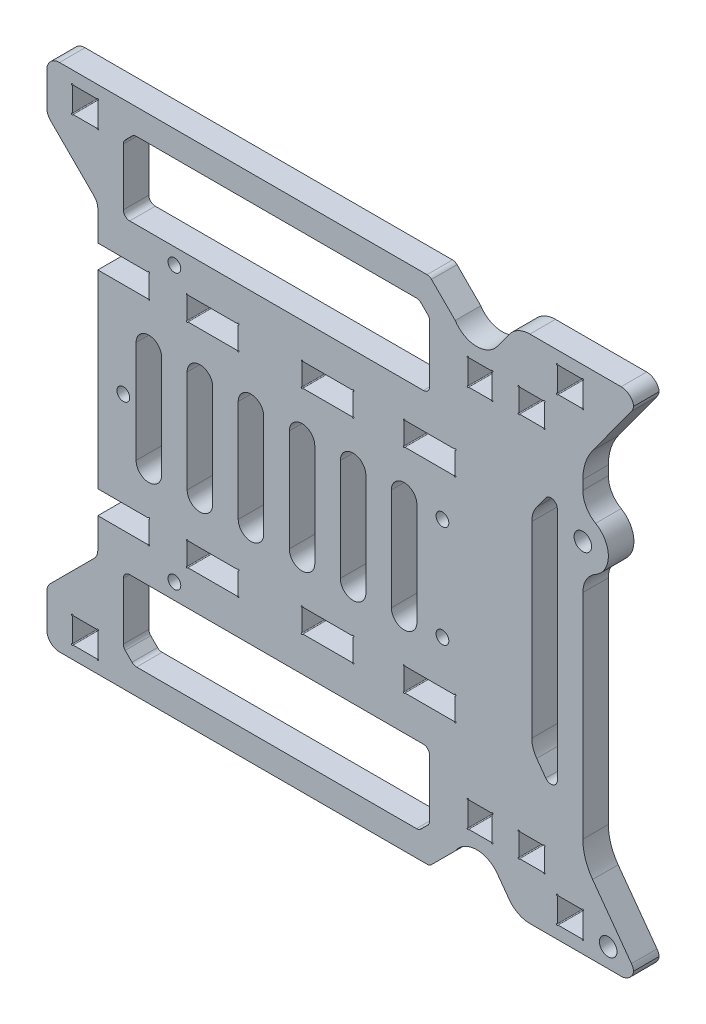
SolidWorks part; units mm, degrees
ref_plane "Front Plane" through (0, 0, 0) normal (0, 0, 1) x (1, 0, 0)
ref_plane "Top Plane" through (0, 0, 0) normal (0, 1, 0) x (1, 0, 0)
ref_plane "Right Plane" through (0, 0, 0) normal (1, 0, 0) x (0, 0, -1)
sketch "Sketch1" plane through (0, 0, 0) normal (0, 0, 1) x (1, 0, 0)
  line L0 (83.672, 0) -> (-43.8164, 0) construction
  line L1 (10.525, 38.1) -> (10.525, -38.1) construction
  line L2 (-27.575, 38.1) -> (48.625, 38.1)
  line L3 (99.425, -63.5) -> (99.425, -60.325)
  line L4 (99.425, -60.325) -> (74.025, -25.4)
  line L5 (-27.575, -63.5) -> (48.625, -63.5)
  line L6 (-27.575, 38.1) -> (-27.575, 54.5197)
  line L7 (48.625, 38.1) -> (48.625, 54.5197)
  line L8 (-24.9447, 57.15) -> (45.9947, 57.15)
  line L9 (-27.575, 63.5) -> (48.625, 63.5)
  line L10 (-33.925, 57.15) -> (-33.925, -57.15)
  line L11 (-27.575, 63.5) -> (-33.925, 57.15)
  line L12 (-24.9447, 57.15) -> (-27.575, 54.5197)
  line L13 (99.425, 63.5) -> (99.425, 60.325)
  line L14 (-23.0849, 59.0099) -> (-29.4349, 52.6599) construction
  line L15 (99.425, 60.325) -> (74.025, 25.4)
  line L16 (74.025, 25.4) -> (74.025, -25.4)
  line L17 (48.625, -38.1) -> (48.625, -54.5197)
  line L18 (-27.575, -38.1) -> (48.625, -38.1)
  line L19 (-24.9447, -57.15) -> (45.9947, -57.15)
  line L20 (-24.9447, -57.15) -> (-27.575, -54.5197)
  line L21 (-27.575, -38.1) -> (-27.575, -54.5197)
  line L22 (-27.575, -63.5) -> (-33.925, -57.15)
  line L23 (48.625, -63.5) -> (54.975, -57.15)
  line L24 (48.625, 63.5) -> (54.975, 57.15)
  line L25 (70.3271, -63.5) -> (99.425, -63.5)
  line L26 (45.9947, 57.15) -> (48.625, 54.5197)
  line L27 (45.9947, -57.15) -> (48.625, -54.5197)
  line L28 (70.3271, 63.5) -> (65.7089, 57.15)
  line L29 (70.3271, 63.5) -> (99.425, 63.5)
  line L30 (78.8831, 75.2646) -> (53.4831, 40.3396) construction
  line L31 (54.975, -42.3909) -> (54.975, -57.15)
  line L32 (70.3271, -63.5) -> (65.7089, -57.15)
  line L34 (48.625, -63.5) -> (54.975, -57.15)
  line L35 (65.7089, 57.15) -> (54.975, 42.3909)
  line L36 (54.975, 42.3909) -> (54.975, 57.15)
  line L37 (65.7089, -57.15) -> (54.975, -42.3909)
  point P7 (-27.575, 0)
  point P21 (74.025, 0)
  point P22 (-33.925, 0)
  dimension "D1" = 25.4
  dimension "D2" = 76.2
  dimension "D3" = 127
  dimension "D4" = 6.35
  dimension "D7" = 3.175
  dimension "D8" = 25.4
  dimension "D9" = 25.4
  dimension "D6" = 6.35
extrude "Boss-Extrude1" add sketch "Sketch1" along normal blind 6.35
fillet "Fillet1" radius 6.35 4 edges at (70.3271, 63.5, 3.175) (70.3271, -63.5, 3.175) (54.975, -42.3909, 3.175) (54.975, 42.3909, 3.175)
fillet "Fillet3" radius 3.175 4 edges at (99.425, 63.5, 3.175) (99.425, 60.325, 3.175) (99.425, -60.325, 3.175) (99.425, -63.5, 3.175)
fillet "Fillet4" radius 6.35 2 edges at (74.025, -25.4, 3.175) (74.025, 25.4, 3.175)
fillet "Fillet7" radius 1.5875 4 edges at (-27.575, -38.1, 3.175) (48.625, -38.1, 3.175) (48.625, 38.1, 3.175) (-27.575, 38.1, 3.175)
fillet "Fillet8" radius 1.5875 2 edges at (48.625, -63.5, 3.175) (48.625, 63.5, 3.175)
fillet "Fillet9" radius 1.5875 8 edges at (-27.575, 54.5197, 3.175) (-24.9447, 57.15, 3.175) (-27.575, -54.5197, 3.175) (-24.9447, -57.15, 3.175) (45.9947, -57.15, 3.175) (48.625, -54.5197, 3.175) (48.625, 54.5197, 3.175) (45.9947, 57.15, 3.175)
sketch "Sketch2" plane through (0, 0, 6.35) normal (0, 0, 1) x (1, 0, 0)
  line L0 (-33.925, 0) -> (74.025, 0) construction
  line L1 (-33.925, 57.15) -> (-33.925, -57.15) construction
  line L2 (74.025, 23.3351) -> (74.025, -23.3351) construction
  line L3 (48.625, 39.6875) -> (48.625, 53.8622) construction
  line L4 (58.3484, 50.8) -> (63.9714, 50.8)
  line L5 (58.15, 50.6016) -> (58.15, 44.6484)
  line L6 (58.3484, 44.45) -> (63.9714, 44.45)
  line L7 (64.1698, 50.6016) -> (64.1698, 44.6484)
  line L8 (64.1698, -50.6016) -> (64.1698, -44.6484)
  line L9 (58.3484, -50.8) -> (63.9714, -50.8)
  line L10 (58.15, -50.6016) -> (58.15, -44.6484)
  line L11 (58.3484, -44.45) -> (63.9714, -44.45)
  arc A0 (58.3484, 50.8) -> (58.15, 50.6016) centre (58.15, 50.8) ccw
  arc A1 (64.1698, 50.6016) -> (63.9714, 50.8) centre (64.1698, 50.8) ccw
  arc A2 (63.9714, 44.45) -> (64.1698, 44.6484) centre (64.1698, 44.45) ccw
  arc A3 (58.15, 44.6484) -> (58.3484, 44.45) centre (58.15, 44.45) ccw
  arc A4 (63.9714, -44.45) -> (64.1698, -44.6484) centre (64.1698, -44.45) cw
  arc A5 (64.1698, -50.6016) -> (63.9714, -50.8) centre (64.1698, -50.8) cw
  arc A6 (58.3484, -50.8) -> (58.15, -50.6016) centre (58.15, -50.8) cw
  arc A7 (58.15, -44.6484) -> (58.3484, -44.45) centre (58.15, -44.45) cw
  point P10 (48.625, 46.7748)
  dimension "D5" = 0.3969
  dimension "D6" = 0.3969
  dimension "D7" = 0.3969
  dimension "D8" = 0.3969
  dimension "D1" = 6.0198
  dimension "D2" = 6.35
  dimension "D3" = 50.8
  dimension "D4" = 9.525
extrude "Cut-Extrude1" cut sketch "Sketch2" against normal through all
sketch "Sketch5" plane through (0, 0, 6.35) normal (0, 0, 1) x (1, 0, 0)
  line L0 (-33.925, 29.3675) -> (74.025, 29.3675) construction
  line L1 (-33.925, 57.15) -> (-33.925, -57.15) construction
  line L2 (74.025, 23.3351) -> (74.025, -23.3351) construction
  line L3 (-25.9875, 38.1) -> (47.0375, 38.1) construction
  line L4 (-33.925, 23.5763) -> (74.025, 23.5763) construction
  line L5 (-33.925, 0) -> (74.025, 0) construction
  line L6 (-11.5016, 29.3675) -> (0.8016, 29.3675)
  line L7 (-11.7, 29.169) -> (-11.7, 23.7747)
  line L8 (-11.5016, 23.5763) -> (0.8016, 23.5763)
  line L9 (1, 29.169) -> (1, 23.7747)
  line L10 (42.4734, 29.3675) -> (54.7766, 29.3675)
  line L11 (42.275, 29.169) -> (42.275, 23.7747)
  line L12 (42.4734, 23.5763) -> (54.7766, 23.5763)
  line L13 (54.975, 29.169) -> (54.975, 23.7747)
  line L14 (29.3766, 29.3675) -> (17.0734, 29.3675)
  line L15 (29.575, 29.169) -> (29.575, 23.7747)
  line L16 (29.3766, 23.5763) -> (17.0734, 23.5763)
  line L17 (16.875, 29.169) -> (16.875, 23.7747)
  line L18 (-21.4234, 29.3675) -> (-33.925, 29.3675)
  line L19 (-21.225, 29.169) -> (-21.225, 23.7747)
  line L20 (-21.4234, 23.5763) -> (-33.925, 23.5763)
  line L21 (-33.925, 29.3675) -> (-33.925, 23.5763)
  line L22 (-33.925, -29.3675) -> (-33.925, -23.5763)
  line L23 (-21.4234, -23.5763) -> (-33.925, -23.5763)
  line L24 (-21.225, -29.169) -> (-21.225, -23.7747)
  line L25 (-21.4234, -29.3675) -> (-33.925, -29.3675)
  line L26 (16.875, -29.169) -> (16.875, -23.7747)
  line L27 (29.3766, -23.5763) -> (17.0734, -23.5763)
  line L28 (29.575, -29.169) -> (29.575, -23.7747)
  line L29 (29.3766, -29.3675) -> (17.0734, -29.3675)
  line L30 (54.975, -29.169) -> (54.975, -23.7747)
  line L31 (42.4734, -23.5763) -> (54.7766, -23.5763)
  line L32 (42.275, -29.169) -> (42.275, -23.7747)
  line L33 (42.4734, -29.3675) -> (54.7766, -29.3675)
  line L34 (1, -29.169) -> (1, -23.7747)
  line L35 (-11.5016, -23.5763) -> (0.8016, -23.5763)
  line L36 (-11.7, -29.169) -> (-11.7, -23.7747)
  line L37 (-11.5016, -29.3675) -> (0.8016, -29.3675)
  line L38 (-33.925, 26.4719) -> (54.975, 26.4719) construction
  arc A0 (-21.225, 29.169) -> (-21.4234, 29.3675) centre (-21.225, 29.3675) ccw
  arc A1 (-11.5016, 29.3675) -> (-11.7, 29.169) centre (-11.7, 29.3675) ccw
  arc A2 (1, 29.169) -> (0.8016, 29.3675) centre (1, 29.3675) ccw
  arc A3 (29.575, 29.169) -> (29.3766, 29.3675) centre (29.575, 29.3675) ccw
  arc A4 (17.0734, 29.3675) -> (16.875, 29.169) centre (16.875, 29.3675) ccw
  arc A5 (54.975, 29.169) -> (54.7766, 29.3675) centre (54.975, 29.3675) ccw
  arc A6 (42.4734, 29.3675) -> (42.275, 29.169) centre (42.275, 29.3675) ccw
  arc A7 (17.0734, 23.5763) -> (16.875, 23.7747) centre (16.875, 23.5763) cw
  arc A8 (29.575, 23.7747) -> (29.3766, 23.5763) centre (29.575, 23.5763) cw
  arc A9 (42.4734, 23.5763) -> (42.275, 23.7747) centre (42.275, 23.5763) cw
  arc A10 (54.975, 23.7747) -> (54.7766, 23.5763) centre (54.975, 23.5763) cw
  arc A11 (1, 23.7747) -> (0.8016, 23.5763) centre (1, 23.5763) cw
  arc A12 (-11.5016, 23.5763) -> (-11.7, 23.7747) centre (-11.7, 23.5763) cw
  arc A13 (-21.225, 23.7747) -> (-21.4234, 23.5763) centre (-21.225, 23.5763) cw
  arc A14 (-21.225, -23.7747) -> (-21.4234, -23.5763) centre (-21.225, -23.5763) ccw
  arc A15 (-11.5016, -23.5763) -> (-11.7, -23.7747) centre (-11.7, -23.5763) ccw
  arc A16 (1, -23.7747) -> (0.8016, -23.5763) centre (1, -23.5763) ccw
  arc A17 (54.975, -23.7747) -> (54.7766, -23.5763) centre (54.975, -23.5763) ccw
  arc A18 (42.4734, -23.5763) -> (42.275, -23.7747) centre (42.275, -23.5763) ccw
  arc A19 (29.575, -23.7747) -> (29.3766, -23.5763) centre (29.575, -23.5763) ccw
  arc A20 (17.0734, -23.5763) -> (16.875, -23.7747) centre (16.875, -23.5763) ccw
  arc A21 (42.4734, -29.3675) -> (42.275, -29.169) centre (42.275, -29.3675) cw
  arc A22 (54.975, -29.169) -> (54.7766, -29.3675) centre (54.975, -29.3675) cw
  arc A23 (17.0734, -29.3675) -> (16.875, -29.169) centre (16.875, -29.3675) cw
  arc A24 (29.575, -29.169) -> (29.3766, -29.3675) centre (29.575, -29.3675) cw
  arc A25 (1, -29.169) -> (0.8016, -29.3675) centre (1, -29.3675) cw
  arc A26 (-11.5016, -29.3675) -> (-11.7, -29.169) centre (-11.7, -29.3675) cw
  arc A27 (-21.225, -29.169) -> (-21.4234, -29.3675) centre (-21.225, -29.3675) cw
  dimension "D11" = 0.3969
  dimension "D12" = 0.3969
  dimension "D13" = 0.3969
  dimension "D14" = 0.3969
  dimension "D15" = 0.3969
  dimension "D16" = 0.3969
  dimension "D17" = 0.3969
  dimension "D1" = 8.7325
  dimension "D3" = 12.7
  dimension "D4" = 12.7
  dimension "D5" = 41.275
  dimension "D6" = 34.925
  dimension "D7" = 12.7
  dimension "D8" = 12.7
  dimension "D9" = 50.8
  dimension "D10" = 0
  dimension "D2" = 5.7912
extrude "Cut-Extrude4" cut sketch "Sketch5" against normal through all
sketch "Sketch6" plane through (0, 0, 6.35) normal (0, 0, 1) x (1, 0, 0)
  line L0 (80.375, 34.1312) -> (80.375, -34.1312)
  line L1 (98.8177, 59.49) -> (75.2395, 27.07) construction
  line L2 (98.8177, -59.49) -> (75.2395, -27.07) construction
  line L3 (74.025, 23.3351) -> (74.025, -23.3351) construction
  line L4 (86.725, 34.1312) -> (86.725, -34.1312)
  line L5 (86.725, 34.1312) -> (86.725, 42.8625)
  line L6 (86.725, 42.8625) -> (80.375, 34.1312)
  line L7 (86.725, -34.1312) -> (86.725, -42.8625)
  line L8 (86.725, -42.8625) -> (80.375, -34.1312)
  dimension "D1" = 6.35
  dimension "D2" = 6.35
extrude "Boss-Extrude2" add sketch "Sketch6" against normal blind 6.35
fillet "Fillet10" radius 1.5875 2 edges at (80.375, -34.1312, 3.175) (80.375, 34.1312, 3.175)
fillet "Fillet11" radius 12.7 2 edges at (86.725, 42.8625, 3.175) (86.725, -42.8625, 3.175)
hole_wizard "11/64 (0.17188) Diameter Hole1" positions "Sketch8" profile "Sketch7" hole size "11/64" standard "ANSI Inch" end condition through all
sketch "Sketch8" plane through (0, 0, 6.35) normal (0, 0, 1) x (1, 0, 0)
  line L1 (-33.925, -29.3675) -> (-33.925, -57.15) construction
  line L2 (73.5606, 63.5) -> (96.25, 63.5) construction
  point P0 (86.725, 25.4)
  dimension "D1" = 38.1
  dimension "D2" = 120.65
sketch "Sketch7" plane through (86.725, 25.4, 6.35) normal (1, 0, 0) x (0, -1, 0)
  line L0 (0, 0) -> (0, 6.35)
  line L1 (0, 6.35) -> (2.1829, 6.35)
  line L2 (2.1829, 6.35) -> (2.1829, 0)
  line L5 (2.1829, 0) -> (0, 0)
  line L11 (0, -6.35) -> (0, 107.95) construction
  dimension "Thru Hole Dia." = 4.3658
  dimension "Thru Hole Depth" = 6.35
sketch "Sketch10" plane through (0, 0, 6.35) normal (0, 0, 1) x (1, 0, 0)
  line L0 (51.8, 63.5) -> (51.8, -63.5) construction
  line L1 (-27.575, 63.5) -> (47.9674, 63.5) construction
  line L2 (-27.575, -63.5) -> (47.9674, -63.5) construction
  line L3 (23.225, 29.3675) -> (23.225, -29.3675) construction
  line L4 (29.3766, 29.3675) -> (17.0734, 29.3675) construction
  line L5 (17.0734, -29.3675) -> (29.3766, -29.3675) construction
  line L6 (-27.575, 63.5) -> (-27.575, -63.5) construction
  line L7 (-33.925, 0) -> (74.025, 0) construction
  line L8 (-33.925, 23.5763) -> (-33.925, -23.5763) construction
  line L9 (74.025, 23.3351) -> (74.025, -23.3351) construction
  circle A0 centre (51.8, 12.7) radius 1.5875
  circle A1 centre (51.8, -12.7) radius 1.5875
  circle A2 centre (-27.575, 0) radius 1.5875
  dimension "D3" = 3.175
  dimension "D5" = 79.375
  dimension "D1" = 28.575
  dimension "D2" = 79.375
  dimension "D4" = 12.7
extrude "Cut-Extrude6" cut sketch "Sketch10" against normal through all
sketch "Sketch11" plane through (0, 0, 6.35) normal (0, 0, 1) x (1, 0, 0)
  line L0 (-62.0481, -60.325) -> (124.8486, -60.325) construction
  line L1 (-27.575, -63.5) -> (47.9674, -63.5) construction
  line L2 (-27.575, -63.5) -> (-33.925, -57.15)
  line L3 (-33.925, -57.15) -> (-33.925, -50.8)
  line L4 (-33.925, -50.8) -> (-33.925, -38.1)
  line L5 (-46.625, -50.8) -> (-46.625, -63.5)
  line L6 (-46.625, -63.5) -> (-27.575, -63.5)
  line L7 (-46.625, -50.8) -> (-33.925, -38.1)
  line L8 (-33.925, -29.3675) -> (-33.925, -57.15) construction
  line L9 (-46.625, 63.5) -> (-27.575, 63.5)
  line L10 (-33.925, 0) -> (74.025, 0) construction
  line L11 (-46.625, 50.8) -> (-46.625, 63.5)
  line L12 (-33.925, 23.5763) -> (-33.925, -23.5763) construction
  line L13 (74.025, 23.3351) -> (74.025, -23.3351) construction
  line L14 (-46.625, 50.8) -> (-33.925, 38.1)
  line L15 (-33.925, 57.15) -> (-33.925, 50.8)
  line L16 (-27.575, 63.5) -> (-33.925, 57.15)
  line L17 (-33.925, 50.8) -> (-33.925, 38.1)
  point P2 (10.1962, -63.5)
  dimension "D1" = 3.175
  dimension "D2" = 12.7
  dimension "D3" = 12.7
extrude "Boss-Extrude4" add sketch "Sketch11" against normal blind 6.35
sketch "Sketch12" plane through (0, 0, 6.35) normal (0, 0, 1) x (1, 0, 0)
  line L0 (73.5606, -63.5) -> (96.25, -63.5) construction
  line L1 (86.5266, -60.325) -> (80.5734, -60.325)
  line L2 (86.725, -60.1266) -> (86.725, -54.1734)
  line L3 (86.5266, -53.975) -> (80.5734, -53.975)
  line L4 (80.375, -60.1266) -> (80.375, -54.1734)
  line L5 (-33.925, -29.3675) -> (-33.925, -38.1) construction
  line L6 (-33.925, 0) -> (74.025, 0) construction
  line L7 (86.725, 60.1266) -> (86.725, 54.1734)
  line L8 (86.5266, 60.325) -> (80.5734, 60.325)
  line L9 (80.375, 60.1266) -> (80.375, 54.1734)
  line L10 (86.5266, 53.975) -> (80.5734, 53.975)
  line L11 (83.55, -60.325) -> (-33.7266, -60.325) construction
  line L12 (-34.1234, -60.325) -> (-54.5439, -60.325) construction
  line L13 (-34.1234, -60.325) -> (-40.0766, -60.325)
  line L14 (-33.925, -60.1266) -> (-33.925, -54.1734)
  line L15 (-34.1234, -53.975) -> (-40.0766, -53.975)
  line L16 (-40.275, -60.1266) -> (-40.275, -54.1734)
  line L17 (-34.1234, 60.325) -> (-40.0766, 60.325)
  line L18 (-33.925, 60.1266) -> (-33.925, 54.1734)
  line L19 (-40.275, 60.1266) -> (-40.275, 54.1734)
  line L20 (-34.1234, 53.975) -> (-40.0766, 53.975)
  arc A0 (-40.275, 60.1266) -> (-40.0766, 60.325) centre (-40.275, 60.325) cw
  arc A1 (80.5734, -53.975) -> (80.375, -54.1734) centre (80.375, -53.975) ccw
  arc A2 (86.725, -54.1734) -> (86.5266, -53.975) centre (86.725, -53.975) ccw
  arc A3 (80.375, -60.1266) -> (80.5734, -60.325) centre (80.375, -60.325) ccw
  arc A4 (86.5266, -60.325) -> (86.725, -60.1266) centre (86.725, -60.325) ccw
  arc A5 (86.5266, 60.325) -> (86.725, 60.1266) centre (86.725, 60.325) cw
  arc A6 (80.375, 60.1266) -> (80.5734, 60.325) centre (80.375, 60.325) cw
  arc A7 (80.5734, 53.975) -> (80.375, 54.1734) centre (80.375, 53.975) cw
  arc A8 (86.725, 54.1734) -> (86.5266, 53.975) centre (86.725, 53.975) cw
  arc A9 (-40.0766, -53.975) -> (-40.275, -54.1734) centre (-40.275, -53.975) ccw
  arc A10 (-33.925, -54.1734) -> (-34.1234, -53.975) centre (-33.925, -53.975) ccw
  arc A11 (-34.1234, -60.325) -> (-33.925, -60.1266) centre (-33.925, -60.325) ccw
  arc A12 (-40.275, -60.1266) -> (-40.0766, -60.325) centre (-40.275, -60.325) ccw
  arc A13 (-34.1234, 60.325) -> (-33.925, 60.1266) centre (-33.925, 60.325) cw
  arc A14 (-33.925, 54.1734) -> (-34.1234, 53.975) centre (-33.925, 53.975) cw
  arc A15 (-40.0766, 53.975) -> (-40.275, 54.1734) centre (-40.275, 53.975) cw
  point P4 (84.9053, -63.5)
  dimension "D5" = 0.3969
  dimension "D6" = 0.3969
  dimension "D7" = 0.3969
  dimension "D8" = 0.3969
  dimension "D12" = 0.3969
  dimension "D13" = 0.3969
  dimension "D14" = 0.3969
  dimension "D15" = 0.3969
  dimension "D1" = 6.35
  dimension "D2" = 6.35
  dimension "D3" = 3.175
  dimension "D4" = 114.3
  dimension "D9" = 6.35
  dimension "D10" = 6.35
  dimension "D11" = 120.65
extrude "Cut-Extrude7" cut sketch "Sketch12" against normal blind 6.35
fillet "Fillet12" radius 3.175 6 edges at (-46.625, 63.5, 3.175) (-46.625, 50.8, 3.175) (-33.925, 38.1, 3.175) (-46.625, -63.5, 3.175) (-46.625, -50.8, 3.175) (-33.925, -38.1, 3.175)
hole_wizard "11/64 (0.17188) Diameter Hole2" positions "Sketch14" profile "Sketch13" hole size "11/64" standard "ANSI Inch" end condition through all
sketch "Sketch14" plane through (0, 0, 0) normal (0, 0, -1) x (-1, 0, 0)
  line L0 (-73.5606, -63.5) -> (-96.25, -63.5) construction
  point P0 (-93.0328, -58.7375)
  dimension "D1" = 4.7625
  dimension "D2" = 6.35
sketch "Sketch13" plane through (93.0328, -58.7375, 0) normal (1, 0, 0) x (0, 1, 0)
  line L0 (0, 0) -> (0, 6.35)
  line L1 (0, 6.35) -> (2.1829, 6.35)
  line L2 (2.1829, 6.35) -> (2.1829, 0)
  line L5 (2.1829, 0) -> (0, 0)
  line L11 (0, -6.35) -> (0, 107.95) construction
  dimension "Thru Hole Dia." = 4.3658
  dimension "Thru Hole Depth" = 6.35
sketch "Sketch15" plane through (0, 0, 6.35) normal (0, 0, 1) x (1, 0, 0)
  line L0 (-33.925, 0) -> (45.45, 0) construction
  line L1 (-33.925, 23.5763) -> (-33.925, -23.5763) construction
  line L3 (-21.225, -12.7) -> (-21.225, 12.7) construction
  line L4 (-24.4, -12.7) -> (-24.4, 12.7)
  line L5 (-18.05, -12.7) -> (-18.05, 12.7)
  line L6 (-8.525, -12.7) -> (-8.525, 12.7) construction
  line L7 (-11.7, -12.7) -> (-11.7, 12.7)
  line L8 (-5.35, -12.7) -> (-5.35, 12.7)
  line L9 (4.175, -12.7) -> (4.175, 12.7) construction
  line L10 (1, -12.7) -> (1, 12.7)
  line L11 (7.35, -12.7) -> (7.35, 12.7)
  line L12 (16.875, -12.7) -> (16.875, 12.7) construction
  line L13 (13.7, -12.7) -> (13.7, 12.7)
  line L14 (20.05, -12.7) -> (20.05, 12.7)
  line L15 (29.575, -12.7) -> (29.575, 12.7) construction
  line L16 (26.4, -12.7) -> (26.4, 12.7)
  line L17 (32.75, -12.7) -> (32.75, 12.7)
  line L18 (42.275, -12.7) -> (42.275, 12.7) construction
  line L19 (39.1, -12.7) -> (39.1, 12.7)
  line L20 (45.45, -12.7) -> (45.45, 12.7)
  arc A0 (-24.4, -12.7) -> (-18.05, -12.7) centre (-21.225, -12.7) ccw
  arc A1 (-18.05, 12.7) -> (-24.4, 12.7) centre (-21.225, 12.7) ccw
  arc A2 (-11.7, -12.7) -> (-5.35, -12.7) centre (-8.525, -12.7) ccw
  arc A3 (-5.35, 12.7) -> (-11.7, 12.7) centre (-8.525, 12.7) ccw
  arc A4 (1, -12.7) -> (7.35, -12.7) centre (4.175, -12.7) ccw
  arc A5 (7.35, 12.7) -> (1, 12.7) centre (4.175, 12.7) ccw
  arc A6 (13.7, -12.7) -> (20.05, -12.7) centre (16.875, -12.7) ccw
  arc A7 (20.05, 12.7) -> (13.7, 12.7) centre (16.875, 12.7) ccw
  arc A8 (26.4, -12.7) -> (32.75, -12.7) centre (29.575, -12.7) ccw
  arc A9 (32.75, 12.7) -> (26.4, 12.7) centre (29.575, 12.7) ccw
  arc A10 (39.1, -12.7) -> (45.45, -12.7) centre (42.275, -12.7) ccw
  arc A11 (45.45, 12.7) -> (39.1, 12.7) centre (42.275, 12.7) ccw
  point P8 (-21.225, 0)
  point P17 (-8.525, 0)
  point P24 (4.175, 0)
  point P31 (16.875, 0)
  point P38 (29.575, 0)
  point P43 (42.275, 0)
  dimension "D1" = 12.7
  dimension "D2" = 6
extrude "Cut-Extrude8" cut sketch "Sketch15" against normal through all
sketch "Sketch16" plane through (0, 0, 6.35) normal (0, 0, 1) x (1, 0, 0)
  line L0 (73.5606, 63.5) -> (96.25, 63.5) construction
  line L1 (76.9593, 50.8) -> (71.0062, 50.8)
  line L2 (77.1578, 50.6016) -> (77.1578, 45.1564)
  line L3 (76.9593, 44.958) -> (71.0062, 44.958)
  line L4 (70.8078, 50.6016) -> (70.8078, 45.1564)
  line L8 (70.8078, -50.6016) -> (70.8078, -45.1564)
  line L9 (76.9593, -44.958) -> (71.0062, -44.958)
  line L10 (77.1578, -50.6016) -> (77.1578, -45.1564)
  line L11 (76.9593, -50.8) -> (71.0062, -50.8)
  arc A0 (71.0062, 50.8) -> (70.8078, 50.6016) centre (70.8078, 50.8) ccw
  arc A1 (77.1578, 50.6016) -> (76.9593, 50.8) centre (77.1578, 50.8) ccw
  arc A2 (76.9593, 44.958) -> (77.1578, 45.1564) centre (77.1578, 44.958) ccw
  arc A3 (70.8078, 45.1564) -> (71.0062, 44.958) centre (70.8078, 44.958) ccw
  arc A4 (70.8078, -45.1564) -> (71.0062, -44.958) centre (70.8078, -44.958) cw
  arc A5 (76.9593, -44.958) -> (77.1578, -45.1564) centre (77.1578, -44.958) cw
  arc A6 (77.1578, -50.6016) -> (76.9593, -50.8) centre (77.1578, -50.8) cw
  arc A7 (71.0062, -50.8) -> (70.8078, -50.6016) centre (70.8078, -50.8) cw
  dimension "D5" = 0.3969
  dimension "D6" = 0.3969
  dimension "D7" = 0.3969
  dimension "D8" = 0.3969
  dimension "D1" = 6.35
  dimension "D2" = 5.842
  dimension "D3" = 22.225
  dimension "D4" = 12.7
extrude "Cut-Extrude9" cut sketch "Sketch16" against normal through all
sketch "Sketch17" plane through (0, 0, 6.35) normal (0, 0, 1) x (1, 0, 0)
  circle A0 centre (86.725, 25.4) radius 6.35
  circle A1 centre (86.725, 25.4) radius 2.1829
extrude "Boss-Extrude5" add sketch "Sketch17" against normal up to surface (6.35 mm away) up to face at (73.9828, -47.879, 0)
fillet "Fillet13" radius 6.35 1 edges at (86.725, 31.75, 3.175)
sketch "Sketch19" plane through (0, 0, 0) normal (0, 0, -1) x (-1, 0, 0)
  line L0 (25.9875, -38.1) -> (-47.0375, -38.1) construction
  line L1 (33.925, -29.3675) -> (33.925, -36.7849) construction
  line L2 (33.925, 0) -> (0, 0) construction
  line L3 (33.925, 23.5763) -> (33.925, -23.5763) construction
  circle A0 centre (14.875, -34.1313) radius 1.5875
  circle A1 centre (14.875, 34.1313) radius 1.5875
  dimension "D1" = 3.175
  dimension "D2" = 3.9688
  dimension "D3" = 19.05
extrude "Cut-Extrude10" cut sketch "Sketch19" against normal through all
